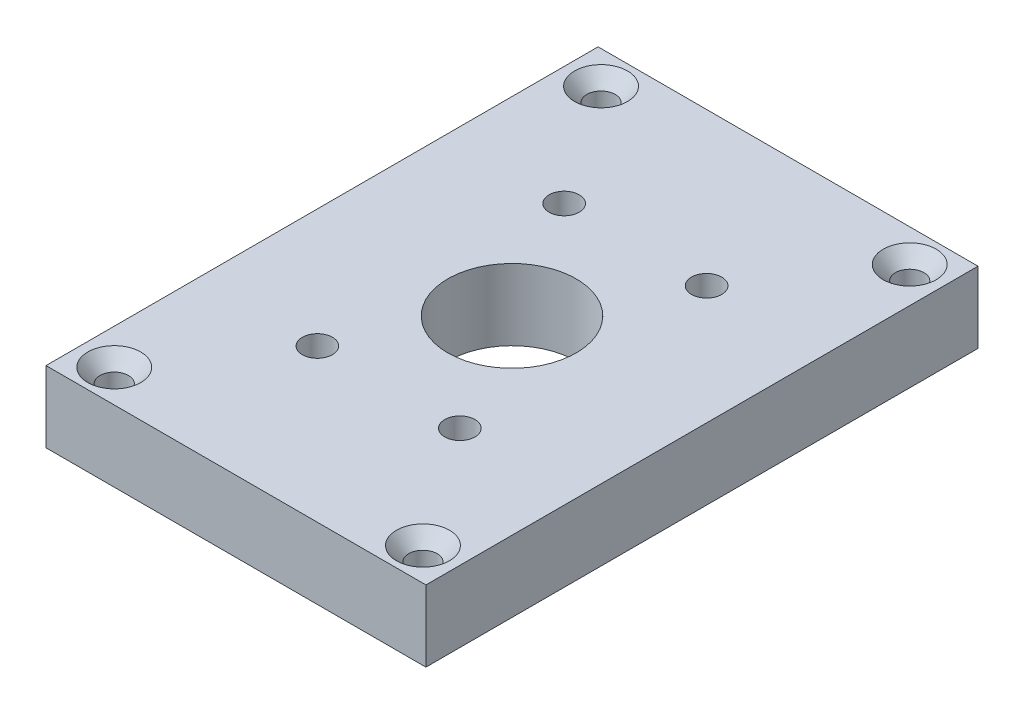
SolidWorks part; units mm, degrees
ref_plane "Front Plane" through (0, 0, 0) normal (0, 0, 1) x (1, 0, 0)
ref_plane "Top Plane" through (0, 0, 0) normal (0, 1, 0) x (1, 0, 0)
ref_plane "Right Plane" through (0, 0, 0) normal (1, 0, 0) x (0, 0, -1)
sketch "Sketch1" plane through (0, 0, 0) normal (0, 1, 0) x (1, 0, 0)
  line L0 (-25.4, -37.3063) -> (25.4, -37.3063) construction
  line L1 (-25.4, -36.9094) -> (25.4, -36.9094)
  line L2 (-25.4, -36.9094) -> (-25.4, 36.9094)
  line L3 (-25.4, 36.9094) -> (25.4, 36.9094)
  line L4 (25.4, -36.9094) -> (25.4, 36.9094)
  line L5 (-25.4, -36.9094) -> (25.4, 36.9094) construction
  line L6 (-25.4, 36.9094) -> (25.4, -36.9094) construction
  point P0 (0, 0)
  dimension "D1" = 0.3969
extrude "Boss-Extrude1" add sketch "Sketch1" along normal blind 9.525
hole_wizard "CSK for #6 Flat Head Machine Screw1" positions "Sketch3" profile "Sketch2" countersink size "#6" standard "Ansi Inch" end condition through all
sketch "Sketch3" plane through (0, 9.525, 0) normal (0, 1, 0) x (-1, 0, 0)
  point P1 (20.6375, -32.5437)
  point P4 (-20.6375, -32.5437)
  point P7 (-20.6375, 32.5438)
  point P10 (20.6375, 32.5438)
sketch "Sketch2" plane through (-20.6375, 9.525, -32.5437) normal (1, 0, 0) x (0, 0, 1)
  line L0 (0, 0) -> (0, 9.525)
  line L1 (0, 9.525) -> (1.8986, 9.525)
  line L2 (1.8986, 9.525) -> (1.8986, 1.892)
  line L3 (1.8986, 1.892) -> (3.5433, 0)
  line L5 (3.5433, 0) -> (0, 0)
  line L6 (-1.8986, 1.892) -> (-3.5433, 0) construction
  line L11 (0, -6.35) -> (0, 107.95) construction
  dimension "Thru Hole Dia." = 3.7973
  dimension "Thru Hole Depth" = 9.525
  dimension "Near C'Sink Dia." = 7.0866
  dimension "Near C'Sink Angle" = 82
sketch "Sketch4" plane through (0, 0, 0) normal (0, -1, 0) x (-1, 0, 0)
  line L0 (-11.1125, 34.6075) -> (11.1125, 34.6075)
  line L1 (-11.1125, -32.4231) -> (11.1125, -32.4231)
  line L2 (-17.4625, -26.0731) -> (-17.4625, 26.0731)
  line L3 (-11.1125, 32.4231) -> (11.1125, 32.4231)
  line L4 (17.4625, -26.0731) -> (17.4625, 26.0731)
  line L5 (-17.4625, -32.4231) -> (17.4625, 32.4231) construction
  line L6 (-17.4625, 32.4231) -> (17.4625, -32.4231) construction
  line L7 (19.6469, -26.0731) -> (19.6469, 26.0731)
  line L8 (-11.1125, -34.6075) -> (11.1125, -34.6075)
  line L9 (-19.6469, -26.0731) -> (-19.6469, 26.0731)
  arc A0 (-11.1125, -32.4231) -> (-17.4625, -26.0731) centre (-11.1125, -26.0731) cw
  arc A1 (11.1125, -32.4231) -> (17.4625, -26.0731) centre (11.1125, -26.0731) ccw
  arc A2 (11.1125, 32.4231) -> (17.4625, 26.0731) centre (11.1125, 26.0731) cw
  arc A3 (-17.4625, 26.0731) -> (-11.1125, 32.4231) centre (-11.1125, 26.0731) cw
  arc A4 (11.1125, 34.6075) -> (19.6469, 26.0731) centre (11.1125, 26.0731) cw
  arc A5 (11.1125, -34.6075) -> (19.6469, -26.0731) centre (11.1125, -26.0731) ccw
  arc A6 (-11.1125, -34.6075) -> (-19.6469, -26.0731) centre (-11.1125, -26.0731) cw
  arc A7 (-19.6469, 26.0731) -> (-11.1125, 34.6075) centre (-11.1125, 26.0731) cw
  point P0 (0, 0)
  dimension "D1" = 6.35
  dimension "D2" = 2.1844
  dimension "D3" = 22.225
  dimension "D4" = 52.1462
extrude "Cut-Extrude1 - dash 036" cut sketch "Sketch4" against normal blind 1.3208
sketch "Sketch5" plane through (0, 9.525, 0) normal (0, 1, 0) x (1, 0, 0)
  line L0 (25.4, 36.9094) -> (-25.4, 36.9094) construction
  circle A4 centre (0, 0) radius 8.5852
  point P3 (0, 36.9094)
extrude "Cut-Extrude1" cut sketch "Sketch5" against normal through all
sketch "Sketch8" plane through (0, 9.525, 0) normal (0, 1, 0) x (-1, 0, 0)
  line L0 (31.6062, 0) -> (-30.5429, 0) construction
  line L1 (0, 0) -> (-8.0091, -13.8721) construction
  circle A0 centre (0, 0) radius 19.05 construction
  point P5 (-9.525, -16.4978)
  dimension "D1" = 38.1
  dimension "D2" = 60
hole_wizard "#10-32 Tapped Hole2" positions "Sketch10" profile "Sketch9" tap size "#10-32" standard "Ansi Inch"
sketch "Sketch10" plane through (0, 9.525, 0) normal (0, 1, 0) x (-1, 0, 0)
  point P1 (-9.525, -16.4978)
sketch "Sketch9" plane through (9.525, 9.525, -16.4978) normal (1, 0, 0) x (0, 0, 1)
  line L0 (0, 0) -> (0, 7.5633)
  line L1 (0, 7.5633) -> (2.0193, 6.35)
  line L2 (2.0193, 6.35) -> (2.0193, 0)
  line L5 (2.0193, 0) -> (0, 0)
  line L10 (0, 7.5633) -> (-2.0193, 6.35) construction
  line L11 (0, -6.35) -> (0, 107.95) construction
  dimension "Tap Drill Dia." = 4.0386
  dimension "Tap Drill Depth" = 6.35
  dimension "Drill Angle" = 118
pattern_circular "CirPattern1" count 6 over 360 about axis through (0, 9.525, 0) along (0, 1, 0) skipping 2, 5 of "#10-32 Tapped Hole2"
